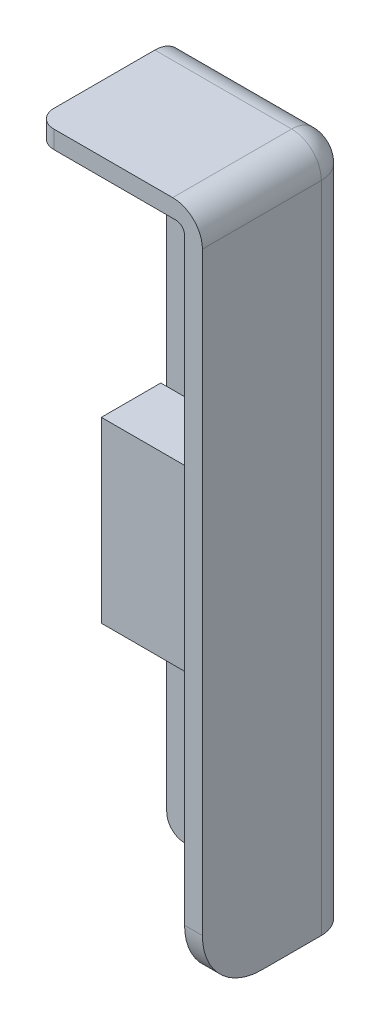
SolidWorks part; units mm, degrees
material "ABS"
ref_plane "Front" through (0, 0, 0) normal (0, 0, 1) x (1, 0, 0)
ref_plane "Top" through (0, 0, 0) normal (0, 1, 0) x (1, 0, 0)
ref_plane "Right" through (0, 0, 0) normal (1, 0, 0) x (0, 0, -1)
sketch "Sketch1" plane through (0, 0, 0) normal (1, 0, 0) x (0, 0, -1)
  line L1 (-12.5, 57.5) -> (12.5, 57.5)
  line L2 (-12.5, 57.5) -> (-12.5, -57.5)
  line L3 (-12.5, -57.5) -> (12.5, -57.5)
  line L4 (12.5, 57.5) -> (12.5, -57.5)
  line L5 (-12.5, 57.5) -> (12.5, -57.5) construction
  line L6 (-12.5, -57.5) -> (12.5, 57.5) construction
  point P0 (0, 0)
  dimension "D1" = 25
  dimension "D2" = 115
extrude "Boss-Extrude1" add sketch "Sketch1" along normal mid plane 28
sketch "Sketch3" plane through (-14, 0, 0) normal (1, 0, 0) x (0, 0, -1)
  line L1 (-12.5, -57.5) -> (9.5, -57.5)
  line L2 (-12.5, -57.5) -> (-12.5, 54.5)
  line L3 (-12.5, 54.5) -> (9.5, 54.5)
  line L4 (9.5, -57.5) -> (9.5, 54.5)
  dimension "D1" = 22
  dimension "D2" = 112
extrude "Cut-Extrude1" cut sketch "Sketch3" along normal offset from surface (25 mm away) 3 up to face at (14, 0, 0)
sketch "Sketch4" plane through (11, 0, 0) normal (-1, 0, 0) x (0, 0, 1)
  line L0 (12.5, -1.5) -> (-9.5, -1.5) construction
  line L1 (12.5, 54.5) -> (12.5, -57.5) construction
  line L2 (-9.5, -57.5) -> (-9.5, 54.5) construction
  line L4 (-3.5, 13.5) -> (6.5, 13.5)
  line L5 (-3.5, 13.5) -> (-3.5, -16.5)
  line L6 (-3.5, -16.5) -> (6.5, -16.5)
  line L7 (6.5, 13.5) -> (6.5, -16.5)
  line L8 (-3.5, 13.5) -> (6.5, -16.5) construction
  line L9 (-3.5, -16.5) -> (6.5, 13.5) construction
  point P6 (1.5, -1.5)
  dimension "D1" = 30
  dimension "D2" = 10
extrude "Boss-Extrude2" add sketch "Sketch4" along normal blind 20
hole_wizard "#2 Clearance Hole1" positions "Sketch5" profile "Sketch6" hole size "#2" standard "ANSI Inch"
sketch "Sketch5" plane through (-9, 0, 0) normal (-1, 0, 0) x (0, 0, 1)
  line L0 (1.5, 13.5) -> (1.5, -16.5) construction
  line L1 (6.5, 13.5) -> (-3.5, 13.5) construction
  line L2 (-3.5, -16.5) -> (6.5, -16.5) construction
  line L4 (-3.5, -1.5) -> (6.5, -1.5) construction
  line L5 (-3.5, 13.5) -> (-3.5, -16.5) construction
  line L6 (6.5, -16.5) -> (6.5, 13.5) construction
  point P0 (1.5, 8.5)
  point P2 (1.5, -11.5)
  dimension "D1" = 10
  dimension "D2" = 10
sketch "Sketch6" plane through (-9, 8.5, 1.5) normal (0, 1, 0) x (0, 0, 1)
  line L0 (0, 0) -> (0, 7.0292)
  line L1 (0, 7.0292) -> (1.1303, 6.35)
  line L2 (1.1303, 6.35) -> (1.1303, 0)
  line L5 (1.1303, 0) -> (0, 0)
  line L10 (0, 7.0292) -> (-1.1303, 6.35) construction
  line L11 (0, -6.35) -> (0, 107.95) construction
  dimension "Hole Dia." = 2.2606
  dimension "Hole Depth" = 6.35
  dimension "Drill Angle" = 118
fillet "Fillet1" radius 1.5 3 edges at (11, -1.5, -9.5) (-1.5, 54.5, -9.5) (11, 54.5, 1.5)
fillet "Fillet3" radius 5 3 edges at (0, 57.5, -12.5) (14, 57.5, 0) (14, 0, -12.5)
fillet "Fillet4" radius 10 1 edges at (12.5, -57.5, 12.5)
fillet "Fillet5" radius 3 2 edges at (-14, -57.5, -11) (-14, 56, 12.5)
fillet "Fillet6" radius 3 4 edges at (11, 13.5, 1.5) (11, -1.5, -3.5) (11, -16.5, 1.5) (11, -1.5, 6.5)
